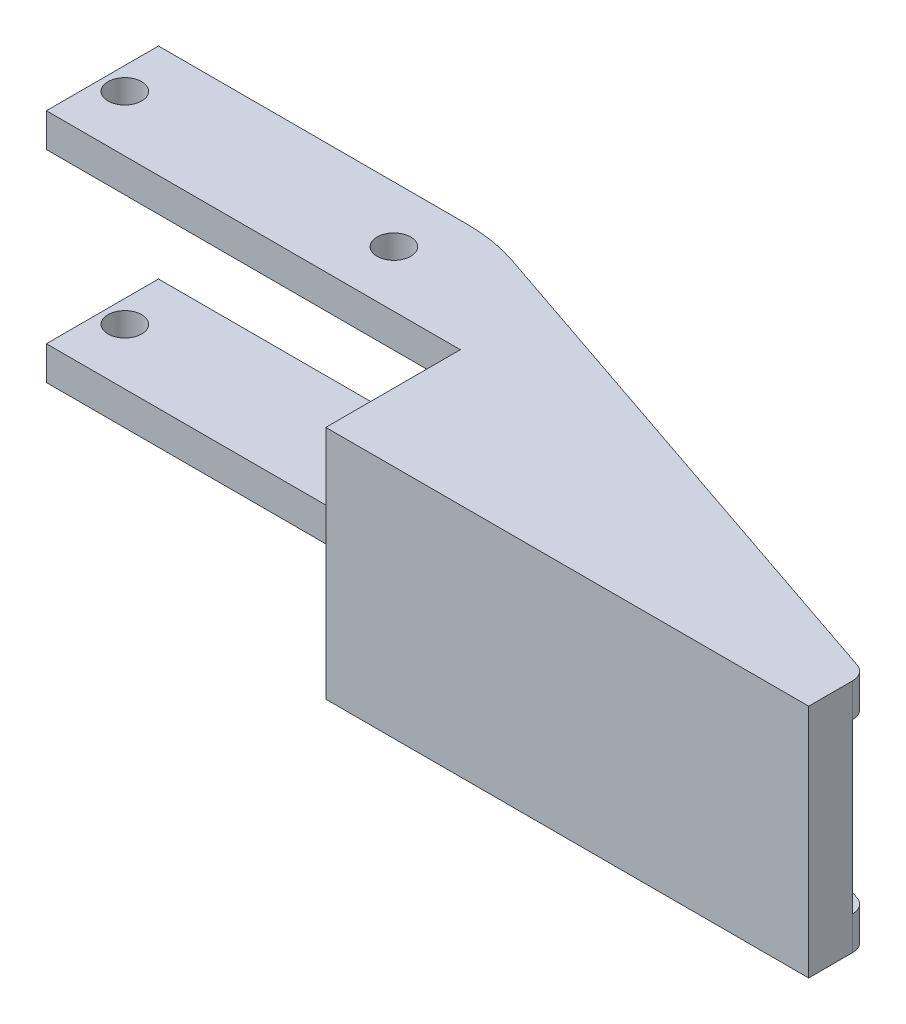
SolidWorks part; units mm, degrees
material "ABS"
ref_plane "Front Plane" through (0, 0, 0) normal (0, 0, 1) x (1, 0, 0)
ref_plane "Top Plane" through (0, 0, 0) normal (0, 1, 0) x (1, 0, 0)
ref_plane "Right Plane" through (0, 0, 0) normal (1, 0, 0) x (0, 0, -1)
sketch "Sketch1" plane through (0, 0, 0) normal (0, 1, 0) x (1, 0, 0)
  line L0 (-4.5779, 9.3563) -> (42.0567, -6.4995)
  line L1 (-36.9262, 10.1547) -> (-9.4065, 10.1547)
  line L2 (-36.9262, 10.1547) -> (-36.9262, 0.1547)
  line L3 (0, -11.8453) -> (43.0738, -11.8453)
  line L4 (43.0738, -7.9196) -> (43.0738, -11.8453)
  line L5 (-36.9262, 10.1547) -> (43.0738, -11.8453) construction
  line L6 (-3.5929, 0.1547) -> (26.2671, -1.131) construction
  line L10 (-36.9262, 0.1547) -> (0, 0.1547)
  line L11 (0, -11.8453) -> (0, 0.1547)
  arc A0 (-9.4065, 10.1547) -> (-4.5779, 9.3563) centre (-9.4065, -4.8453) cw
  arc A1 (42.0567, -6.4995) -> (43.0738, -7.9196) centre (41.5738, -7.9196) cw
  point P0 (0, 0)
  point P10 (-6.9262, 10.1547)
  point P13 (43.0738, -6.8453)
  dimension "D6" = 15
  dimension "D7" = 1.5
  dimension "D1" = 10
  dimension "D2" = 80
  dimension "D3" = 5
  dimension "D4" = 50
  dimension "D5" = 10.7143
  dimension "D8" = 12
  dimension "D9" = 33.3333
extrude "Boss-Extrude1" add sketch "Sketch1" against normal blind 3
extrude "Boss-Extrude2" add sketch "Sketch1<2>" along normal blind 3 from offset 15 separate body
sketch "Sketch1<2>" plane through (0, 0, 0) normal (0, 1, 0) x (1, 0, 0) same geometry as "Sketch1"
hole_wizard "Ø3.0mm Clearance Dowel Hole1" positions "Sketch2" profile "Sketch3" hole size "Ø3.0" standard "ANSI Metric" end condition through all
sketch "Sketch2" plane through (0, -3, 0) normal (0, -1, 0) x (-1, 0, 0)
  line L0 (36.9262, 10.1547) -> (36.9262, 0.1547) construction
  point P0 (34.9262, 5.1547)
  point P2 (10.9262, 5.1547)
  point P7 (36.9262, 5.1547)
  dimension "D1" = 2
  dimension "D2" = 24
sketch "Sketch3" plane through (-34.9262, -3, -5.1547) normal (1, 0, 0) x (0, 0, -1)
  line L0 (0, 0) -> (0, 21)
  line L1 (0, 21) -> (1.5, 21)
  line L2 (1.5, 21) -> (1.5, 0)
  line L5 (1.5, 0) -> (0, 0)
  line L11 (0, -6.35) -> (0, 107.95) construction
  dimension "Thru Hole Dia." = 3
  dimension "Thru Hole Depth" = 21
sketch "Sketch5" plane through (0, 0, 0) normal (0, 1, 0) x (1, 0, 0)
  line L1 (0, -11.8453) -> (43.0738, -11.8453)
  line L2 (0, -11.8453) -> (0, -7.9196)
  line L3 (0, -7.9196) -> (43.0738, -7.9196)
  line L4 (43.0738, -11.8453) -> (43.0738, -7.9196)
extrude "Boss-Extrude3" add sketch "Sketch5" along normal up to surface (15 mm away) up to face at (-34.9262, 15, -6.6547)
